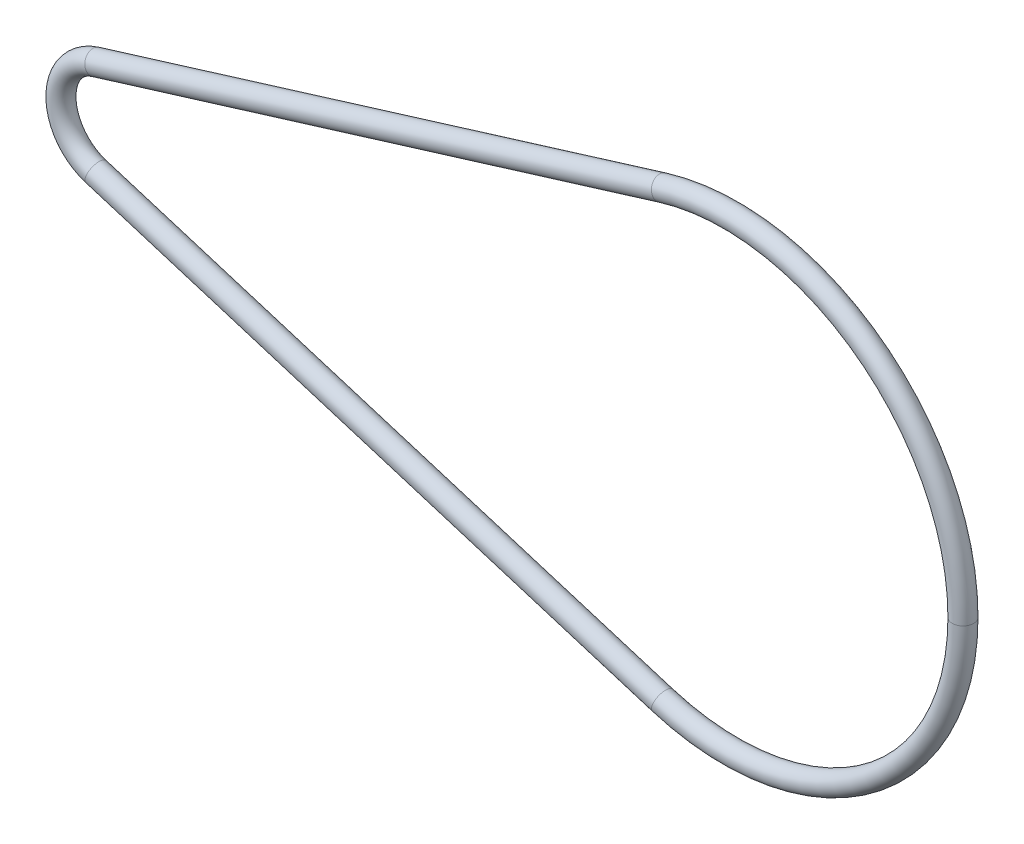
SolidWorks part; units mm, degrees
material "Rubber"
ref_plane "Front Plane" through (0, 0, 0) normal (0, 0, 1) x (1, 0, 0)
ref_plane "Top Plane" through (0, 0, 0) normal (0, 1, 0) x (1, 0, 0)
ref_plane "Right Plane" through (0, 0, 0) normal (1, 0, 0) x (0, 0, -1)
sketch "Sketch1" plane through (0, 0, 0) normal (0, 0, 1) x (1, 0, 0)
  line L0 (-45.2722, 2.6703) -> (-4.6718, 15.172)
  line L1 (-45.2722, -2.6703) -> (-4.6718, -15.172)
  arc A0 (-4.6718, -15.172) -> (-4.6718, 15.172) centre (0, 0) ccw
  arc A1 (-45.2722, 2.6703) -> (-45.2722, -2.6703) centre (-44.45, 0) ccw
  point P9 (-43.3801, -2.581)
  dimension "D1" = 5.588
  dimension "D2" = 31.75
  dimension "D3" = 44.45
sketch "Sketch2" plane through (0, 0, 0) normal (0, 1, 0) x (1, 0, 0)
  circle A0 centre (16.637, 0) radius 0.762
  point P2 (15.875, 0)
  point P3 (0, 0)
  point P4 (0, 0)
  dimension "D1" = 1.524
sweep "Sweep1" add profiles "Sketch2" path "Sketch1"
ref_axis "Axis1" through (0, 0, -0.8382) along (0, 0, 1)
